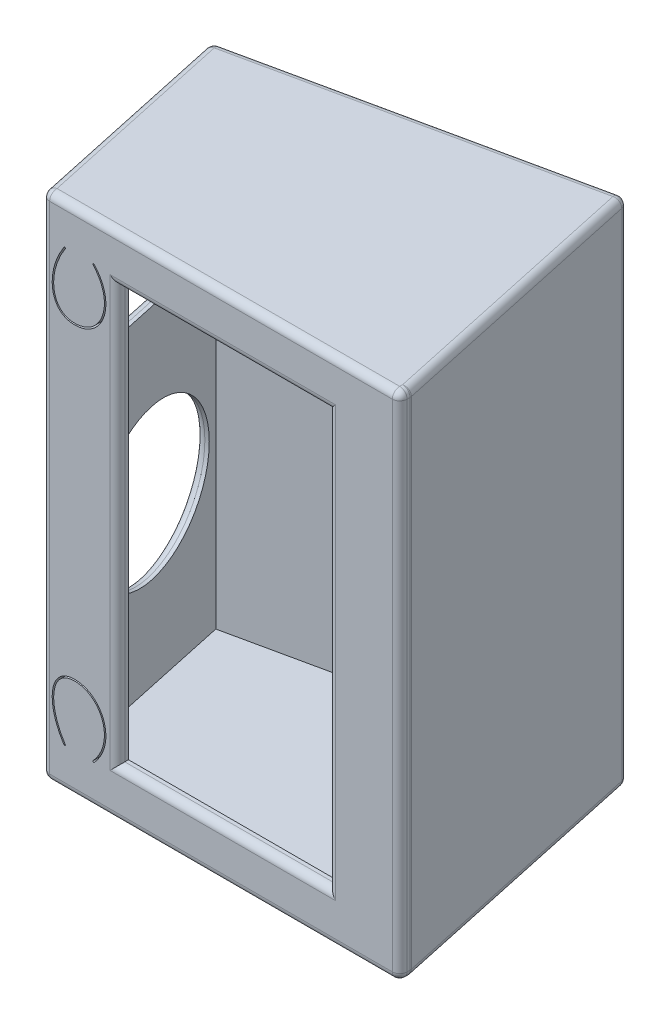
SolidWorks part; units mm, degrees
note: The reader was unsure of these and kept them because the rebuilt part matched: shared geometry of "Sketch2<3>".
ref_plane "Front Plane" through (0, 0, 0) normal (0, 0, 1) x (1, 0, 0)
ref_plane "Top Plane" through (0, 0, 0) normal (0, 1, 0) x (1, 0, 0)
ref_plane "Right Plane" through (0, 0, 0) normal (1, 0, 0) x (0, 0, -1)
sketch "Sketch1" plane through (0, 0, 0) normal (0, 0, 1) x (1, 0, 0)
  line L0 (-14.245, 28.005) -> (14.245, 28.005)
  line L1 (-13.745, 27.505) -> (13.745, 27.505) construction
  line L2 (-13.745, 27.505) -> (-13.745, -27.505) construction
  line L3 (-13.745, -27.505) -> (13.745, -27.505) construction
  line L4 (13.745, 27.505) -> (13.745, -27.505) construction
  line L5 (14.245, 28.005) -> (14.245, -28.005)
  line L6 (-14.245, -28.005) -> (14.245, -28.005)
  line L7 (-14.245, 28.005) -> (-14.245, -28.005)
  line L8 (-15.745, 29.505) -> (15.745, 29.505)
  line L9 (15.745, 29.505) -> (15.745, -29.505)
  line L10 (-15.745, -29.505) -> (15.745, -29.505)
  line L11 (-15.745, 29.505) -> (-15.745, -29.505)
  line L12 (-24.2048, 34.5) -> (23.8953, 34.5)
  line L13 (-22.7048, 33) -> (22.3953, 33)
  line L14 (-22.7048, 33) -> (-22.7048, -33)
  line L15 (-22.7048, -33) -> (22.3953, -33)
  line L16 (22.3953, 33) -> (22.3953, -33)
  line L17 (23.8953, 34.5) -> (23.8953, -34.5)
  line L18 (-24.2048, -34.5) -> (23.8953, -34.5)
  line L19 (-24.2048, 34.5) -> (-24.2048, -34.5)
  line L20 (19.0299, 32.5) -> (1.0299, 32.5) construction
  line L21 (1.0299, -32.5) -> (19.0299, -32.5) construction
  dimension "D4" = 0.5
  dimension "D5" = 0.5
  dimension "D1" = 0.5
  dimension "D2" = 1.5
  dimension "D3" = 1.5
extrude "Boss-Extrude1" add sketch "Sketch1" along normal blind 1.5 contours L16 L13 L14 L15 L11 L8 L9 L10 | L8 L11 L10 L9 L7 L0 L5 L6 | L12 L19 L18 L17 L13 L16 L15 L14
sketch "Sketch2" plane through (-6.6592, 0, -30.9142) normal (-0.2106, 0, -0.9776) x (-0.9776, 0, 0.2106)
  line L0 (-21.8595, 33) -> (22.4779, 33)
  line L1 (-23.3595, -34.5) -> (23.9779, -34.5)
  line L2 (-23.3595, -34.5) -> (-23.3595, 34.5)
  line L3 (-23.3595, 34.5) -> (23.9779, 34.5)
  line L4 (23.9779, -34.5) -> (23.9779, 34.5)
  line L5 (22.4779, -33) -> (22.4779, 33)
  line L6 (-21.8595, -33) -> (22.4779, -33)
  line L7 (-21.8595, -33) -> (-21.8595, 33)
  dimension "D1" = 1.5
extrude "Boss-Extrude2" add sketch "Sketch2" against normal up to next contours L1 L4 L3 L2 L6 L7 L0 L5
extrude "Boss-Extrude3" add sketch "Sketch2<3>" along normal blind 1.5 contours L1 L4 L3 L2
sketch "Sketch2<3>" plane through (-6.6592, 0, -30.9142) normal (-0.2106, 0, -0.9776) x (-0.9776, 0, 0.2106) same geometry as "Sketch2"
sketch "Sketch3" plane through (0, 0, 1.5) normal (0, 0, 1) x (1, 0, 0)
  line L0 (-30.4154, 0) -> (23.8953, 0) construction
  line L1 (-30.4154, -34.5) -> (-30.4154, 34.5) construction
  line L2 (23.8953, 34.5) -> (23.8953, -34.5) construction
  arc A0 (-21.2897, 29.0006) -> (-21.4568, 29.1104) centre (-21.3733, 29.0555) ccw
  arc A1 (-17.5272, 29.0006) -> (-17.3791, 29.135) centre (-17.4532, 29.0678) cw
  arc A2 (-17.5272, -29.0006) -> (-17.3791, -29.135) centre (-17.4532, -29.0678) ccw
  arc A3 (-21.2897, -29.0006) -> (-21.4568, -29.1104) centre (-21.3733, -29.0555) cw
  spline S0 degree 3 poles (-21.2897, 29.0006) (-23.5009, 25.6375) (-23.3143, 20.6532) (-16.2602, 21.1027) (-14.89, 26.0947) (-17.5272, 29.0006) knots 0 0 0 0 0.438563 0.566022 1 1 1 1
  spline S1 degree 1 poles (-21.4568, 29.1104) (-17.3791, 29.135) knots 0 0 1 1 construction
  spline S2 degree 3 poles (-21.4568, 29.1104) (-21.7674, 28.6382) (-22.3273, 27.6179) (-23.0223, 25.633) (-23.1844, 23.2866) (-22.3498, 21.5349) (-21.0464, 20.8018) (-19.8045, 20.6766) (-18.5193, 20.9345) (-17.0502, 21.7813) (-16.0788, 23.2262) (-15.7463, 24.9813) (-15.855, 26.3827) (-16.279, 27.565) (-16.829, 28.4751) (-17.1895, 28.926) (-17.3791, 29.135) knots 0 0 0 0 0.0625 0.125 0.25 0.375 0.4375 0.5 0.5625 0.625 0.75 0.8125 0.875 0.9375 0.96875 1 1 1 1
  spline S3 degree 3 poles (-21.4568, -29.1104) (-21.7674, -28.6382) (-22.3273, -27.6179) (-23.0223, -25.633) (-23.1844, -23.2866) (-22.3498, -21.5349) (-21.0464, -20.8018) (-19.8045, -20.6766) (-18.5193, -20.9345) (-17.0502, -21.7813) (-16.0788, -23.2262) (-15.7463, -24.9813) (-15.855, -26.3827) (-16.279, -27.565) (-16.829, -28.4751) (-17.1895, -28.926) (-17.3791, -29.135) knots 0 0 0 0 0.0625 0.125 0.25 0.375 0.4375 0.5 0.5625 0.625 0.75 0.8125 0.875 0.9375 0.96875 1 1 1 1
  spline S4 degree 3 poles (-21.2897, -29.0006) (-23.5009, -25.6375) (-23.3143, -20.6532) (-16.2602, -21.1027) (-14.89, -26.0947) (-17.5272, -29.0006) knots 0 0 0 0 0.438563 0.566022 1 1 1 1
  dimension "D1" = 0.2
extrude "Cut-Extrude1" cut sketch "Sketch3" against normal up to next contours A3 S4 A2 S3 | S2 A1 S0 A0
sketch "Sketch4" plane through (-23.4402, 0, 5.0493) normal (-0.9776, 0, 0.2106) x (0.2106, 0, 0.9776)
  line L1 (-30.0507, 19.614) -> (-15.8686, 19.614)
  line L2 (-30.0507, 19.614) -> (-30.0507, 11.432)
  line L3 (-30.0507, 11.432) -> (-15.8686, 11.432)
  line L4 (-15.8686, 19.614) -> (-15.8686, 11.432)
  circle A0 centre (-20.3233, -10.4) radius 10.1543
extrude "Cut-Extrude2" cut sketch "Sketch4" against normal up to next
fillet "Fillet1" radius 1 24 edges at (15.8606, 0, -37.2996) (23.8953, 0, 0) (-30.4154, 0, -27.3313) (-24.2048, 0, 1.5) (-28.2751, 11.432, -17.3956) (-26.7819, 15.523, -10.4636) (-28.2751, 19.614, -17.3956) (-29.7683, 15.523, -24.3276) (-25.5816, -10.4, -4.8918) (23.8953, -34.5, 0.75) (19.8779, -34.5, -18.6498) (-7.2774, -34.5, -32.3155) (-27.3101, -34.5, -12.9157) (-0.1547, -34.5, 1.5) (-0.1547, 34.5, 1.5) (-27.3101, 34.5, -12.9157) (-7.2774, 34.5, -32.3155) (19.8779, 34.5, -18.6498) (23.8953, 34.5, 0.75) (-14.245, 0, 1.5) (0, -28.005, 1.5) (0, 28.005, 1.5) (14.245, 0, 1.5) (23.8953, 0, 1.5)
